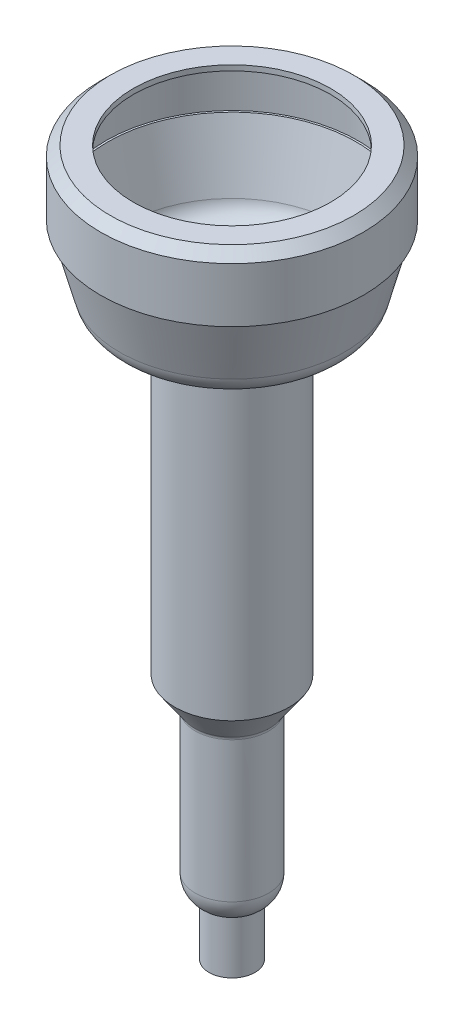
SolidWorks part; units mm, degrees
ref_plane "Front Plane" through (0, 0, 0) normal (0, 0, 1) x (1, 0, 0)
ref_plane "Top Plane" through (0, 0, 0) normal (0, 1, 0) x (1, 0, 0)
ref_plane "Right Plane" through (0, 0, 0) normal (1, 0, 0) x (0, 0, -1)
sketch "Sketch1" plane through (0, 0, 0) normal (0, 0, 1) x (1, 0, 0)
  line L0 (-3.7558, 14.5464) -> (-4.55, 14.5464)
  line L2 (-4.55, 14.5464) -> (-4.8, 14.2964)
  line L3 (-4.8, 14.2964) -> (-4.8, 12.5)
  line L4 (-4.8, 12.5) -> (-4.7262, 12.5)
  line L5 (-4.7262, 12.5) -> (-4.0851, 10.1074)
  line L10 (0, 14.5) -> (0, -4.448) construction
  line L12 (-3.7558, 14.7464) -> (-4.6328, 14.7464)
  line L13 (-4.6328, 14.7464) -> (-5, 14.3792)
  line L14 (-5, 14.3792) -> (-5, 12.3)
  line L15 (-5, 12.3) -> (-4.8797, 12.3)
  line L16 (-4.8797, 12.3) -> (-4.2803, 10.0633)
  line L21 (-3.7558, 14.5464) -> (-3.7558, 14.7464)
  line L26 (-3.349, 9.4896) -> (-2, 9.4896)
  line L27 (-1.78, -2.0758) -> (-1.78, -7.3968) construction
  line L28 (-1.98, -2.2052) -> (-1.98, -7.4946) construction
  line L29 (-1.4294, -7.5536) -> (-0.0465, -7.5536) construction
  line L30 (-1.4512, -7.7536) -> (-0.0465, -7.7536) construction
  line L31 (-3.349, 9.4896) -> (-3.349, -1.3715) construction
  line L32 (-3.549, 9.3113) -> (-3.549, -1.5009) construction
  line L33 (-3.549, 9.3113) -> (-2.18, 9.3113)
  line L34 (-2.18, 9.3113) -> (-2.18, -2.6887)
  line L35 (-2, 9.4896) -> (-2, -2.6319)
  line L36 (-3.349, -1.3715) -> (-1.78, -2.0758) construction
  line L37 (-3.549, -1.5009) -> (-1.98, -2.2052) construction
  line L38 (-2, -2.6319) -> (-1.2562, -3.6942)
  line L39 (-2.18, -2.6887) -> (-1.4362, -3.751)
  line L40 (-1.4, -3.8657) -> (-1.4, -4.8901)
  line L41 (-1.2, -5.0901) -> (0, -5.0901)
  line L42 (-1.22, -3.8089) -> (-1.22, -4.7101)
  line L43 (-1.02, -4.9101) -> (0, -4.9101)
  line L44 (0, -4.9101) -> (0, -5.0901)
  arc A1 (-4.0851, 10.1074) -> (-3.349, 9.4896) centre (-3.3468, 10.2396) ccw
  arc A3 (-4.2803, 10.0633) -> (-3.549, 9.3113) centre (-3.3468, 10.2396) ccw
  arc A5 (-1.4294, -7.5536) -> (-1.78, -7.3968) centre (-1.2039, -6.5794) cw construction
  arc A6 (-1.4512, -7.7536) -> (-1.98, -7.4946) centre (-1.2039, -6.5794) cw construction
  arc A7 (-1.4, -4.8901) -> (-1.2, -5.0901) centre (-1.2, -4.8901) ccw
  arc A8 (-1.22, -4.7101) -> (-1.02, -4.9101) centre (-1.02, -4.7101) ccw
  arc A9 (-1.2562, -3.6942) -> (-1.22, -3.8089) centre (-1.42, -3.8089) cw
  arc A10 (-1.4362, -3.751) -> (-1.4, -3.8657) centre (-1.6, -3.8657) cw
  point P51 (-1.98, -4.7052)
  dimension "D1" = 0.18
  dimension "D3" = 145
  dimension "D9" = 0.2
  dimension "D10" = 0.2
  dimension "D2" = 2
  dimension "D5" = 0.1782
  dimension "D6" = 0.18
  dimension "D7" = 0.18
  dimension "D8" = 0.18
  dimension "D11" = 12
  dimension "D12" = 1.4
  dimension "D4" = 0.2
revolve "Revolve2" add sketch "Sketch1" angle 360 about L10
sketch "Sketch2" plane through (0, -5.0901, 0) normal (0, -1, 0) x (1, 0, 0)
  circle A0 centre (0, 0) radius 1.4 construction
  circle A1 centre (0, 0) radius 1.4
extrude "Boss-Extrude1" add sketch "Sketch2" along normal blind 7 and the other way blind 5
sketch "Sketch3" plane through (0, -12.0901, 0) normal (0, -1, 0) x (1, 0, 0)
  circle A0 centre (0, 0) radius 0.875
  dimension "D1" = 1.75
extrude "Cut-Extrude1" cut sketch "Sketch3" against normal blind 2 flip side to cut
fillet "Fillet1" radius 1 1 edges at (1.4, -10.0901, 0)
